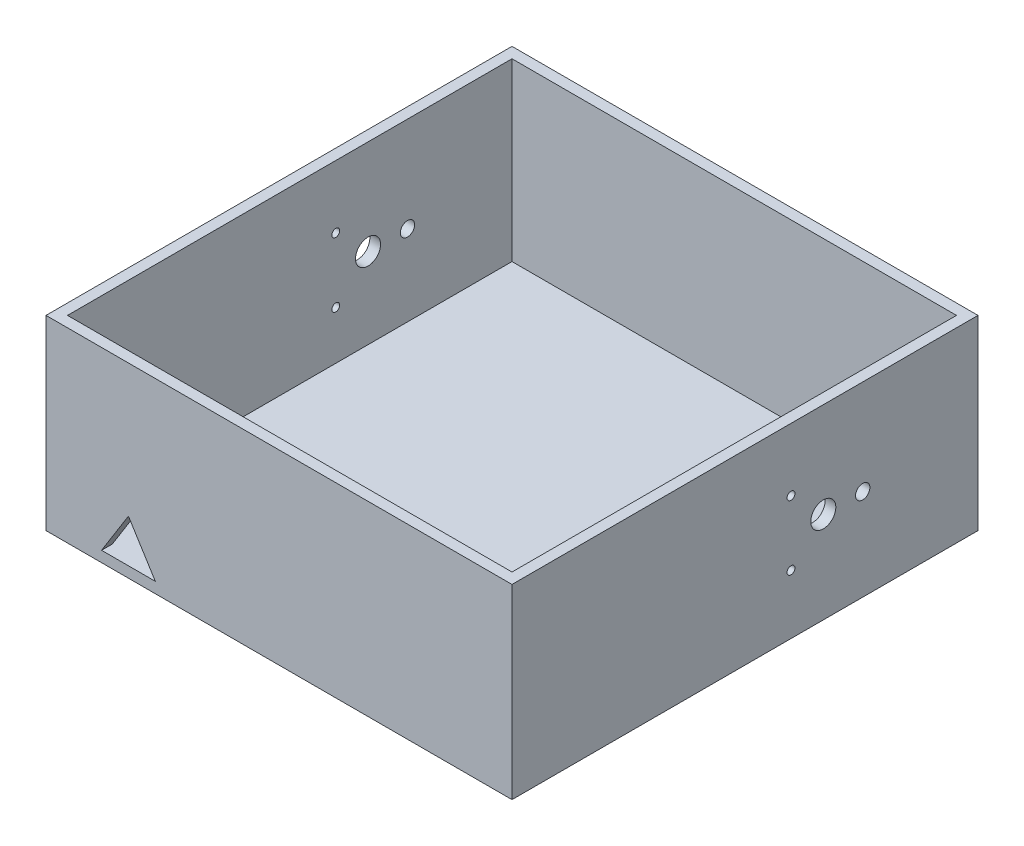
SolidWorks part; units mm, degrees
ref_plane "Front Plane" through (0, 0, 0) normal (0, 0, 1) x (1, 0, 0)
ref_plane "Top Plane" through (0, 0, 0) normal (0, 1, 0) x (1, 0, 0)
ref_plane "Right Plane" through (0, 0, 0) normal (1, 0, 0) x (0, 0, -1)
sketch "Sketch1" plane through (0, 0, 0) normal (0, 1, 0) x (1, 0, 0)
  line L1 (-65, 65) -> (65, 65)
  line L2 (-65, 65) -> (-65, -65)
  line L3 (-65, -65) -> (65, -65)
  line L4 (65, 65) -> (65, -65)
  line L5 (-65, 65) -> (65, -65) construction
  line L6 (-65, -65) -> (65, 65) construction
  point P0 (0, 0)
  dimension "D1" = 130
  dimension "D2" = 130
extrude "Boss-Extrude1" add sketch "Sketch1" along normal blind 52
shell "Shell1" thickness 3 removed face at (0, 52, 0)
sketch "Sketch2" plane through (65, 0, 0) normal (1, 0, 0) x (0, 0, -1)
  line L0 (-65, 0) -> (65, 0) construction
  line L1 (65, 52) -> (65, 0) construction
  circle A0 centre (21.8376, 25.5) radius 3.5
  circle A1 centre (32.8376, 25.5) radius 2
  circle A2 centre (12.8376, 34.5) radius 1.1
  circle A3 centre (12.8376, 16.5) radius 1.1
  point P16 (0, 0)
  dimension "D1" = 7
  dimension "D2" = 4
  dimension "D9" = 2.2
  dimension "D3" = 25.5
  dimension "D4" = 43.1624
  dimension "D5" = 11
  dimension "D6" = 18
  dimension "D7" = 9
  dimension "D8" = 52.1624
extrude "Cut-Extrude1" cut sketch "Sketch2" against normal up to surface (3 mm away) up to face at (62, 27.5, 0)
mirror "Mirror1" about plane through (0, 0, 0) normal (1, 0, 0) of "Cut-Extrude1"
sketch "Sketch3" plane through (0, 3, 0) normal (0, 1, 0) x (1, 0, 0)
  line L0 (-65, -65) -> (65, -65) construction
  line L1 (0, 0) -> (0, -122.9827) construction
  circle A0 centre (-7, -56) radius 1.1
  circle A1 centre (7, -56) radius 1.1
  point P8 (0, 0)
  dimension "D2" = 2.2
  dimension "D1" = 14
  dimension "D3" = 9
extrude "Cut-Extrude2" cut sketch "Sketch3" against normal up to surface (3 mm away) up to face at (0, 0, 0)
sketch "Sketch6" plane through (0, 0, 62) normal (0, 0, -1) x (-1, 0, 0)
  line L0 (34.5, 3) -> (42, 15)
  line L1 (62, 3) -> (-62, 3) construction
  line L2 (42, 15) -> (49.5, 3)
  line L3 (34.5, 3) -> (49.5, 3)
  point P5 (53.9064, 3)
  dimension "D1" = 15
  dimension "D2" = 12
  dimension "D3" = 20
extrude "Cut-Extrude4" cut sketch "Sketch6" against normal up to surface (3 mm away) up to face at (0, 26, 65)
